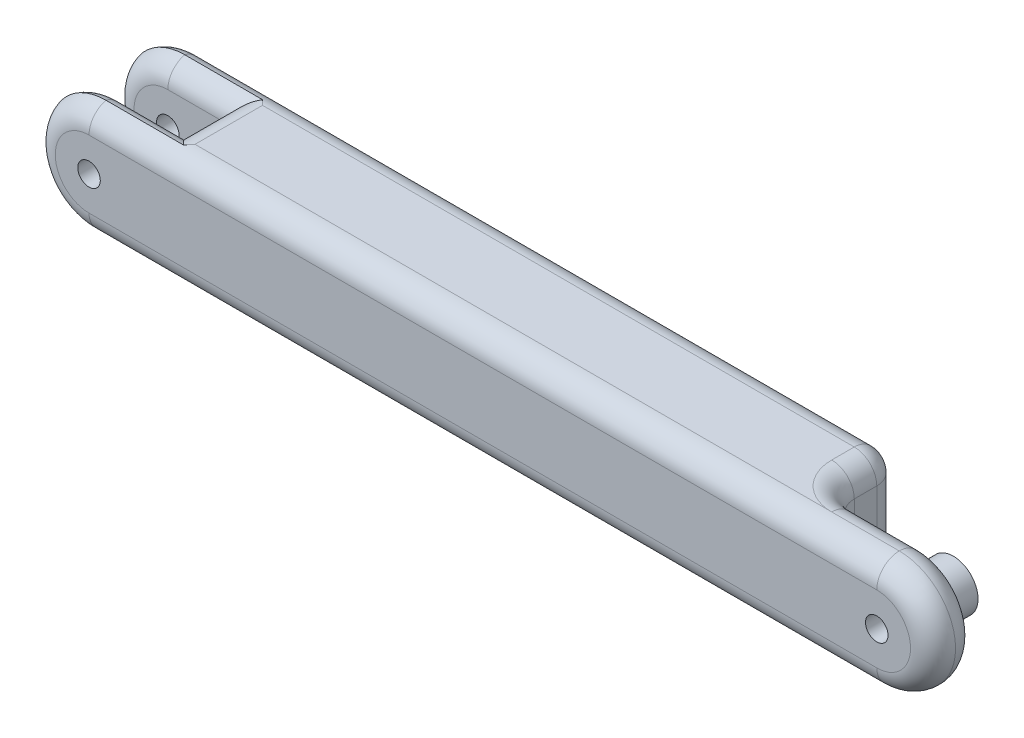
SolidWorks part; units mm, degrees
ref_plane "前视基准面" through (0, 0, 0) normal (0, 0, 1) x (1, 0, 0)
ref_plane "上视基准面" through (0, 0, 0) normal (0, 1, 0) x (1, 0, 0)
ref_plane "右视基准面" through (0, 0, 0) normal (1, 0, 0) x (0, 0, -1)
sketch "草图1" plane through (0, 0, 0) normal (0, 0, 1) x (1, 0, 0)
  line L1 (-13.5, 2.5) -> (21.5, 2.5)
  line L3 (-13.5, -2.5) -> (21.5, -2.5)
  line L5 (-7.8666, 4.1502) -> (20.7795, -10.9627) construction
  line L6 (-8.1245, -0.8431) -> (24.0908, 2.5) construction
  arc A0 (-13.5, 2.5) -> (-13.5, -2.5) centre (-13.5, 0) ccw
  arc A1 (21.5, -2.5) -> (21.5, 2.5) centre (21.5, 0) ccw
  circle A2 centre (-13.5, 0) radius 0.5
  circle A3 centre (21.5, 0) radius 0.5
  point P0 (0, 0)
  dimension "D3" = 5
  dimension "D6" = 5
  dimension "D4" = 1
  dimension "D8" = 1
  dimension "D1" = 35
  dimension "D2" = 5
  dimension "D5" = 2.5
  dimension "D7" = 2.5
extrude "凸台-拉伸1" add sketch "草图1" along normal blind 5
sketch "草图2" plane through (0, 0, 0) normal (0, 0, -1) x (-1, 0, 0)
  circle A0 centre (13.5, 0) radius 3
  dimension "D1" = 6
ref_plane "基准面1" through (0, 0, 2.5) normal (0, 0, -1) x (-1, 0, 0)
extrude "切除-拉伸1" cut sketch "草图2" against normal blind 1 and the other way blind 1 from surface starting at plane "基准面1"
sketch "草图4" plane through (0, 0, 5) normal (0, 0, 1) x (1, 0, 0)
  line L1 (17.5, 2.5) -> (25.5, 2.5)
  line L2 (17.5, 2.5) -> (17.5, -2.5)
  line L3 (17.5, -2.5) -> (25.5, -2.5)
  line L4 (25.5, 2.5) -> (25.5, -2.5)
  line L5 (17.5, 2.5) -> (25.5, -2.5) construction
  line L6 (17.5, -2.5) -> (25.5, 2.5) construction
  point P0 (21.5, 0)
  dimension "D1" = 5
  dimension "D2" = 8
extrude "切除-拉伸2" [suppressed] cut sketch "草图4" against normal blind 2.5
sketch "草图5" [suppressed] plane through (0, 0, 1.5) normal (0, 0, 1) x (1, 0, 0)
  circle A0 centre (16.5, 0) radius 1.5
  circle A1 centre (16.5, 0) radius 1.25
  dimension "D1" = 3
  dimension "D2" = 2.5
extrude "凸台-拉伸2" [suppressed] add sketch "草图5" along normal blind 1
sketch "草图7" plane through (0, 0, 0) normal (0, 0, -1) x (-1, 0, 0)
  line L0 (13.5, -2.5) -> (-21.5, -2.5) construction
  line L1 (-25.5, 2.5) -> (-17.5, 2.5)
  line L2 (-25.5, 2.5) -> (-25.5, -2.5)
  line L3 (-25.5, -2.5) -> (-17.5, -2.5)
  line L4 (-17.5, 2.5) -> (-17.5, -2.5)
  line L5 (-25.5, 2.5) -> (-17.5, -2.5) construction
  line L6 (-25.5, -2.5) -> (-17.5, 2.5) construction
  point P0 (-21.5, 0)
  dimension "D1" = 8
extrude "切除-拉伸3" cut sketch "草图7" against normal blind 3
sketch "草图8" plane through (0, 0, 3) normal (0, 0, -1) x (-1, 0, 0)
  circle A0 centre (-21.5, 0) radius 1.1
  circle A1 centre (-21.5, 0) radius 0.5
  dimension "D1" = 2.2
  dimension "D2" = 1
extrude "凸台-拉伸3" add sketch "草图8" along normal blind 1.4
fillet "圆角1" radius 1 22 edges at (17.5, 2.5, 1.5) (19.5, 2.5, 3) (24, 0, 3) (19.5, -2.5, 3) (-12.6708, -2.5, 1.5) (-12.6708, 2.5, 1.5) (-12.6708, -2.5, 3.5) (-12.6708, 2.5, 3.5) (-16, 0, 5) (4, 2.5, 5) (24, 0, 5) (2, 2.5, 0) (-16, 0, 0) (-16, 0, 1.5) (-16, 0, 3.5) (-11.8417, 2.5, 2.5) (-11.8417, -2.5, 2.5) (4, -2.5, 5) (17.5, -2.5, 1.5) (2, -2.5, 0) (17.5, 0, 3) (17.5, 0, 0)
